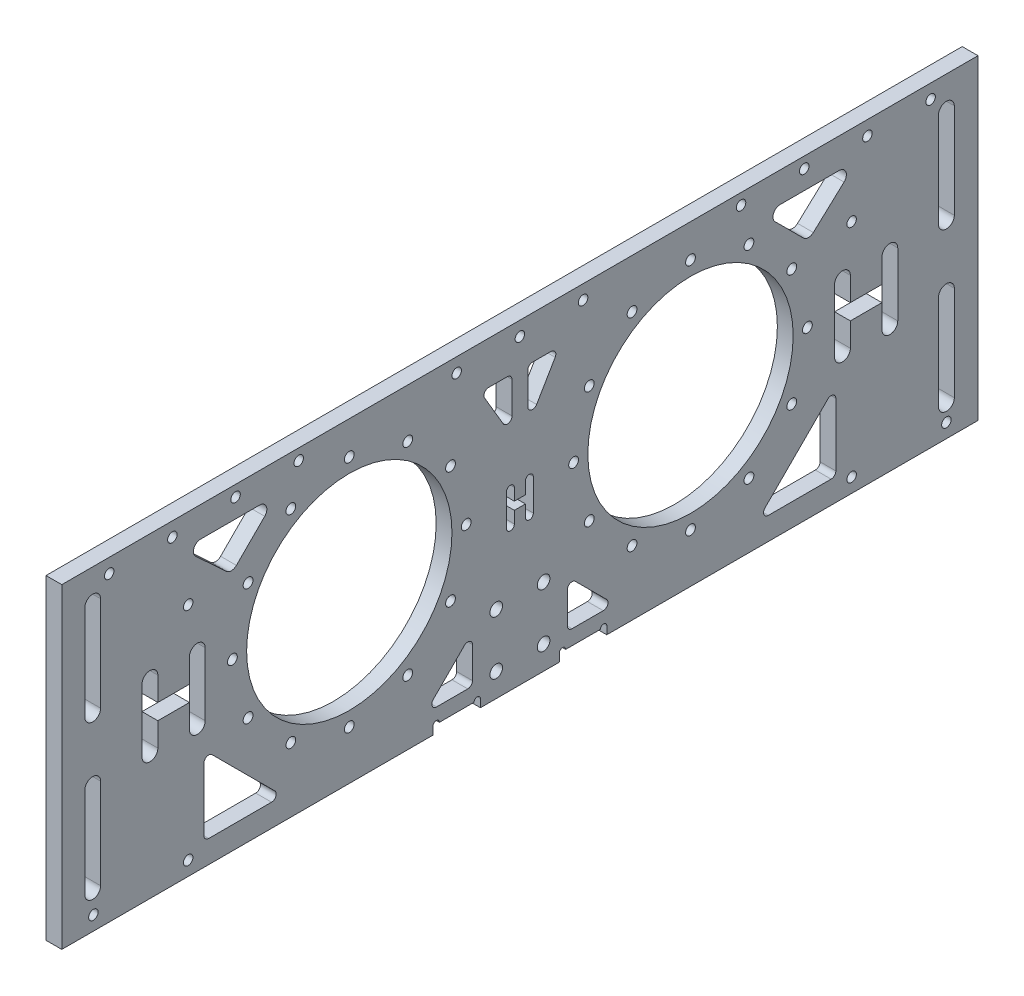
SolidWorks part; units mm, degrees
material "6061 合金"
ref_plane "前视基准面" through (0, 0, 0) normal (0, 0, 1) x (1, 0, 0)
ref_plane "上视基准面" through (0, 0, 0) normal (0, 1, 0) x (1, 0, 0)
ref_plane "右视基准面" through (0, 0, 0) normal (1, 0, 0) x (0, 0, -1)
sketch "草图1" plane through (0, 0, 0) normal (1, 0, 0) x (0, 0, -1)
  line L0 (54, 48) -> (54, -53) construction
  line L1 (-90, -53) -> (198, -53)
  line L2 (-90, -53) -> (-90, 48)
  line L3 (-90, 48) -> (198, 48)
  line L4 (198, -53) -> (198, 48)
  line L5 (-36, 44) -> (-16, 44) construction
  line L6 (46.5, -45) -> (61.5, -45) construction
  line L7 (46.5, -45) -> (46.5, -28) construction
  line L8 (46.5, -28) -> (61.5, -28) construction
  line L9 (61.5, -45) -> (61.5, -28) construction
  line L10 (46.5, -45) -> (61.5, -28) construction
  line L11 (46.5, -28) -> (61.5, -45) construction
  line L12 (144, 44) -> (124, 44) construction
  circle A0 centre (0, 0) radius 32.5
  circle A1 centre (0, 0) radius 37 construction
  circle A2 centre (0, 37) radius 1.55
  circle A3 centre (18.5, 32.0429) radius 1.55
  circle A4 centre (32.0429, 18.5) radius 1.55
  circle A5 centre (37, 0) radius 1.55
  circle A6 centre (32.0429, -18.5) radius 1.55
  circle A7 centre (18.5, -32.0429) radius 1.55
  circle A8 centre (0, -37) radius 1.55
  circle A9 centre (-18.5, -32.0429) radius 1.55
  circle A10 centre (-32.0429, -18.5) radius 1.55
  circle A11 centre (-37, 0) radius 1.55
  circle A12 centre (-32.0429, 18.5) radius 1.55
  circle A13 centre (-18.5, 32.0429) radius 1.55
  circle A14 centre (126.5, 32.0429) radius 1.55
  circle A15 centre (140.0429, 18.5) radius 1.55
  circle A16 centre (145, 0) radius 1.55
  circle A17 centre (140.0429, -18.5) radius 1.55
  circle A18 centre (126.5, -32.0429) radius 1.55
  circle A19 centre (108, -37) radius 1.55
  circle A20 centre (89.5, -32.0429) radius 1.55
  circle A21 centre (75.9571, -18.5) radius 1.55
  circle A22 centre (71, 0) radius 1.55
  circle A23 centre (75.9571, 18.5) radius 1.55
  circle A24 centre (89.5, 32.0429) radius 1.55
  circle A25 centre (108, 37) radius 1.55
  circle A26 centre (108, 0) radius 37 construction
  circle A27 centre (108, 0) radius 32.5
  circle A28 centre (0, 0) radius 46 construction
  circle A29 centre (108, 0) radius 46 construction
  circle A30 centre (61.5, -28) radius 2
  circle A31 centre (46.5, -28) radius 2
  circle A32 centre (46.5, -45) radius 2
  circle A33 centre (61.5, -45) radius 2
  circle A34 centre (-16, 44) radius 1.5
  circle A35 centre (-36, 44) radius 1.5
  circle A36 centre (124, 44) radius 1.5
  circle A37 centre (144, 44) radius 1.5
  point P63 (54, -36.5)
  dimension "D1" = 65
  dimension "D2" = 74
  dimension "D4" = 3.1
  dimension "D9" = 92
  dimension "D13" = 4
  dimension "D17" = 3
  dimension "D5" = 53
  dimension "D6" = 48
  dimension "D7" = 90
  dimension "D8" = 108
  dimension "D10" = 25
  dimension "D11" = 17
  dimension "D12" = 15
  dimension "D14" = 70
  dimension "D15" = 20
  dimension "D16" = 4
  dimension "D3" = 12
extrude "凸台-拉伸1" add sketch "草图1" along normal blind 5
sketch "草图2" plane through (5, 0, 0) normal (1, 0, 0) x (0, 0, -1)
  line L0 (-76, 43) -> (-56, 43) construction
  line L1 (54, 48) -> (54, -53) construction
  line L2 (198, 48) -> (-90, 48) construction
  line L3 (-90, -53) -> (198, -53) construction
  line L4 (184, 43) -> (164, 43) construction
  line L5 (-90, 48) -> (-90, -53) construction
  line L6 (34, 43) -> (54, 43) construction
  circle A0 centre (-76, 43) radius 1.5
  circle A1 centre (-56, 43) radius 1.5
  circle A2 centre (164, 43) radius 1.5
  circle A3 centre (184, 43) radius 1.5
  circle A4 centre (34, 43) radius 1.5
  circle A5 centre (54, 43) radius 1.5
  circle A6 centre (74, 43) radius 1.5
  dimension "D1" = 14
  dimension "D4" = 3
  dimension "D6" = 3
  dimension "D2" = 20
  dimension "D3" = 5
  dimension "D5" = 20
extrude "切除-拉伸1" cut sketch "草图2" against normal through all
sketch "草图3" plane through (5, 0, 0) normal (1, 0, 0) x (0, 0, -1)
  line L0 (-81, -48) -> (-51, -48) construction
  line L1 (-90, 48) -> (-90, -53) construction
  line L2 (-90, -53) -> (198, -53) construction
  line L3 (54, 48) -> (54, -53) construction
  line L4 (198, 48) -> (-90, 48) construction
  line L5 (-81, -48) -> (-81, 22) construction
  line L6 (-81, 22) -> (-51, 22) construction
  line L7 (-51, 22) -> (-51, -48) construction
  line L8 (159, 22) -> (159, -48) construction
  line L9 (189, 22) -> (159, 22) construction
  line L10 (189, -48) -> (189, 22) construction
  line L11 (189, -48) -> (159, -48) construction
  circle A0 centre (-81, -48) radius 1.5
  circle A1 centre (-51, -48) radius 1.5
  circle A2 centre (-81, 22) radius 1.5
  circle A3 centre (-51, 22) radius 1.5
  circle A4 centre (159, 22) radius 1.5
  circle A5 centre (189, 22) radius 1.5
  circle A6 centre (159, -48) radius 1.5
  circle A7 centre (189, -48) radius 1.5
  dimension "D3" = 3
  dimension "D1" = 9
  dimension "D2" = 5
  dimension "D4" = 30
  dimension "D5" = 70
extrude "切除-拉伸2" cut sketch "草图3" against normal blind 10
sketch "草图4" plane through (5, 0, 0) normal (1, 0, 0) x (0, 0, -1)
  line L0 (44.1226, 34) -> (50, 34)
  line L1 (51.5, 32.5) -> (51.5, 22.5085)
  line L2 (48.7071, 21.7479) -> (42.8297, 31.7395)
  line L3 (54, 48) -> (54, -53) construction
  line L4 (198, 48) -> (-90, 48) construction
  line L5 (-90, -53) -> (198, -53) construction
  line L6 (56.5, 32.5) -> (56.5, 22.5085)
  line L7 (63.8774, 34) -> (58, 34)
  line L8 (59.2929, 21.7479) -> (65.1703, 31.7395)
  line L10 (-81, 22) -> (-51, 22) construction
  line L11 (-81, 22) -> (-81, -48) construction
  line L12 (-81, -48) -> (-51, -48) construction
  line L13 (-51, 22) -> (-51, -48) construction
  line L19 (-46, -23.949) -> (-46, -43.8277)
  line L20 (-44.5, -45.3277) -> (-24.6213, -45.3277)
  line L21 (-23.5607, -42.767) -> (-43.4393, -22.8883)
  line L25 (-47.0663, 38) -> (-28.3731, 38)
  line L26 (-26.7654, 34.1187) -> (-35.7353, 25.1488)
  line L27 (-38.8847, 25.0853) -> (-48.608, 34.0552)
  line L34 (27.6213, -45.3277) -> (37.5, -45.3277)
  line L35 (39, -43.8277) -> (39, -33.949)
  line L36 (36.4393, -32.8883) -> (26.5607, -42.767)
  line L37 (71.5607, -32.8883) -> (81.4393, -42.767)
  line L38 (69, -43.8277) -> (69, -33.949)
  line L39 (80.3787, -45.3277) -> (70.5, -45.3277)
  line L40 (159, 22) -> (159, -48) construction
  line L41 (189, -48) -> (159, -48) construction
  line L42 (189, 22) -> (189, -48) construction
  line L43 (189, 22) -> (159, 22) construction
  line L50 (146.8847, 25.0853) -> (156.608, 34.0552)
  line L51 (134.7654, 34.1187) -> (143.7353, 25.1488)
  line L52 (155.0663, 38) -> (136.3731, 38)
  line L56 (131.5607, -42.767) -> (151.4393, -22.8883)
  line L57 (152.5, -45.3277) -> (132.6213, -45.3277)
  line L58 (154, -23.949) -> (154, -43.8277)
  arc A0 (51.5, 22.5085) -> (48.7071, 21.7479) centre (50, 22.5085) cw
  arc A1 (50, 34) -> (51.5, 32.5) centre (50, 32.5) cw
  arc A2 (44.1226, 34) -> (42.8297, 31.7395) centre (44.1226, 32.5) ccw
  arc A3 (58, 34) -> (56.5, 32.5) centre (58, 32.5) ccw
  arc A4 (56.5, 22.5085) -> (59.2929, 21.7479) centre (58, 22.5085) ccw
  arc A5 (63.8774, 34) -> (65.1703, 31.7395) centre (63.8774, 32.5) cw
  arc A14 (-24.6213, -45.3277) -> (-23.5607, -42.767) centre (-24.6213, -43.8277) ccw
  arc A15 (-46, -43.8277) -> (-44.5, -45.3277) centre (-44.5, -43.8277) ccw
  arc A16 (-46, -23.949) -> (-43.4393, -22.8883) centre (-44.5, -23.949) cw
  arc A23 (-28.3731, 38) -> (-26.7654, 34.1187) centre (-28.3731, 35.7264) cw
  arc A24 (-35.7353, 25.1488) -> (-38.8847, 25.0853) centre (-37.343, 26.7565) cw
  arc A25 (-47.0663, 38) -> (-48.608, 34.0552) centre (-47.0663, 35.7264) ccw
  arc A29 (27.6213, -45.3277) -> (26.5607, -42.767) centre (27.6213, -43.8277) cw
  arc A30 (37.5, -45.3277) -> (39, -43.8277) centre (37.5, -43.8277) ccw
  arc A31 (39, -33.949) -> (36.4393, -32.8883) centre (37.5, -33.949) ccw
  arc A32 (69, -33.949) -> (71.5607, -32.8883) centre (70.5, -33.949) cw
  arc A33 (70.5, -45.3277) -> (69, -43.8277) centre (70.5, -43.8277) cw
  arc A34 (80.3787, -45.3277) -> (81.4393, -42.767) centre (80.3787, -43.8277) ccw
  arc A38 (155.0663, 38) -> (156.608, 34.0552) centre (155.0663, 35.7264) cw
  arc A39 (143.7353, 25.1488) -> (146.8847, 25.0853) centre (145.343, 26.7565) ccw
  arc A40 (136.3731, 38) -> (134.7654, 34.1187) centre (136.3731, 35.7264) ccw
  arc A47 (154, -23.949) -> (151.4393, -22.8883) centre (152.5, -23.949) ccw
  arc A48 (154, -43.8277) -> (152.5, -45.3277) centre (152.5, -43.8277) cw
  arc A49 (132.6213, -45.3277) -> (131.5607, -42.767) centre (132.6213, -43.8277) cw
  point P11 (51.5, 17)
  point P14 (51.5, 34)
  point P17 (41.5, 34)
  point P73 (-21, -45.3277)
  point P76 (-46, -45.3277)
  point P79 (-46, -20.3277)
  point P97 (-22.8841, 38)
  point P102 (-52.8841, 38)
  point P105 (-52, 26)
  point P108 (-77, 26)
  point P111 (-77, 38)
  point P115 (24, -45.3277)
  point P118 (39, -45.3277)
  point P130 (69, -45.3277)
  point P131 (84, -45.3277)
  point P199 (185, 38)
  point P200 (185, 26)
  point P201 (160, 26)
  point P202 (160.8841, 38)
  point P203 (130.8841, 38)
  point P207 (154, -20.3277)
  point P208 (154, -45.3277)
  point P209 (129, -45.3277)
  dimension "D5" = 1.5
  dimension "D26" = 1.5
  dimension "D30" = 1.5
  dimension "D1" = 2.5
  dimension "D2" = 14
  dimension "D3" = 10
  dimension "D4" = 17
  dimension "D14" = 5
  dimension "D15" = 25
  dimension "D16" = 25
  dimension "D17" = 10
  dimension "D19" = 25
  dimension "D21" = 45
  dimension "D22" = 30
  dimension "D27" = 15
  dimension "D28" = 45
  dimension "D29" = 15
extrude "切除-拉伸3" cut sketch "草图4" against normal through all
sketch "草图6" plane through (5, 0, 0) normal (1, 0, 0) x (0, 0, -1)
  line L0 (41.5, -53) -> (41.5, -50)
  line L1 (-90, -53) -> (198, -53) construction
  line L5 (54, 48) -> (54, -53) construction
  line L6 (198, 48) -> (-90, 48) construction
  line L7 (39.5, -50) -> (28.5, -50)
  line L8 (26.5, -50) -> (26.5, -53)
  line L9 (26.5, -53) -> (41.5, -53)
  line L13 (81.5, -53) -> (66.5, -53)
  line L14 (81.5, -50) -> (81.5, -53)
  line L15 (68.5, -50) -> (79.5, -50)
  line L16 (66.5, -53) -> (66.5, -50)
  arc A0 (26.5, -50) -> (28.5, -50) centre (27.5, -50) cw
  arc A1 (41.5, -50) -> (39.5, -50) centre (40.5, -50) ccw
  arc A2 (66.5, -50) -> (68.5, -50) centre (67.5, -50) cw
  arc A3 (81.5, -50) -> (79.5, -50) centre (80.5, -50) ccw
  dimension "D4" = 1
  dimension "D1" = 25
  dimension "D2" = 3
  dimension "D3" = 15
extrude "切除-拉伸4" cut sketch "草图6" against normal through all
sketch "草图8" plane through (5, 0, 0) normal (1, 0, 0) x (0, 0, -1)
  line L0 (-90, -53) -> (-91, -53)
  line L1 (-91, -53) -> (-91, 48)
  line L2 (-91, 48) -> (-90, 48)
  line L3 (-90, 48) -> (-90, -53)
  line L4 (198, -53) -> (199, -53)
  line L5 (199, -53) -> (199, 48)
  line L6 (199, 48) -> (198, 48)
  line L7 (198, 48) -> (198, -53)
extrude "凸台-拉伸3" add sketch "草图8" against normal up to surface (5 mm away) up to face at (0, -38.625, -54)
sketch "草图9" plane through (5, 0, 0) normal (1, 0, 0) x (0, 0, -1)
  line L0 (-91, 48) -> (-91, 47.5)
  line L1 (-91, 48) -> (-91, -53) construction
  line L2 (-91, 47.5) -> (199, 47.5)
  line L3 (199, -53) -> (199, 48) construction
  line L4 (199, 47.5) -> (199, 48)
  line L5 (199, 48) -> (-91, 48)
  line L6 (-91, -53) -> (-91, -52.5)
  line L7 (-91, -52.5) -> (199, -52.5)
  line L8 (199, -52.5) -> (199, -53)
  line L9 (199, -53) -> (-91, -53)
extrude "切除-拉伸5" cut sketch "草图9" against normal blind 10
sketch "草图10" plane through (0, 0, 0) normal (-1, 0, 0) x (0, 0, 1)
  line L0 (91, -2.5) -> (81.2144, -2.5)
  line L1 (91, 47.5) -> (91, -52.5) construction
  line L2 (81.2144, -2.5) -> (81.2144, 7.5)
  line L3 (81.2144, -2.5) -> (81.2144, -12.5)
  line L4 (81.2144, 7.5) -> (81.2144, 37.5) construction
  line L5 (78.7144, 7.5) -> (78.7144, 37.5)
  line L6 (83.7144, 7.5) -> (83.7144, 37.5)
  line L7 (81.2144, -12.5) -> (81.2144, -41.1754) construction
  line L8 (83.7144, -12.5) -> (83.7144, -41.1754)
  line L9 (78.7144, -12.5) -> (78.7144, -41.1754)
  line L10 (-199, -2.5) -> (-189, -2.5)
  line L11 (-199, -52.5) -> (-199, 47.5) construction
  line L12 (-189, -2.5) -> (-189, 7.5)
  line L13 (-189, -2.5) -> (-189, -12.5)
  line L14 (-189, 7.5) -> (-189, 37.5) construction
  line L15 (-191.5, 7.5) -> (-191.5, 37.5)
  line L16 (-186.5, 7.5) -> (-186.5, 37.5)
  line L17 (-189, -12.5) -> (-189, -42.5) construction
  line L18 (-186.5, -12.5) -> (-186.5, -42.5)
  line L19 (-191.5, -12.5) -> (-191.5, -42.5)
  arc A0 (78.7144, 7.5) -> (83.7144, 7.5) centre (81.2144, 7.5) ccw
  arc A1 (83.7144, 37.5) -> (78.7144, 37.5) centre (81.2144, 37.5) ccw
  arc A2 (83.7144, -12.5) -> (78.7144, -12.5) centre (81.2144, -12.5) ccw
  arc A3 (78.7144, -41.1754) -> (83.7144, -41.1754) centre (81.2144, -41.1754) ccw
  arc A4 (-191.5, 7.5) -> (-186.5, 7.5) centre (-189, 7.5) ccw
  arc A5 (-186.5, 37.5) -> (-191.5, 37.5) centre (-189, 37.5) ccw
  arc A6 (-186.5, -12.5) -> (-191.5, -12.5) centre (-189, -12.5) ccw
  arc A7 (-191.5, -42.5) -> (-186.5, -42.5) centre (-189, -42.5) ccw
  point P4 (81.2144, 22.5)
  point P12 (81.2144, -26.8377)
  point P24 (-189, 22.5)
  point P30 (-189, -27.5)
  dimension "D1" = 10
  dimension "D2" = 10
  dimension "D3" = 10
  dimension "D4" = 10
  dimension "D5" = 10
extrude "切除-拉伸6" cut sketch "草图10" against normal blind 10 contours L16 A5 L15 A4 | L19 A7 L18 A6 | L6 A1 L5 A0 | L9 A3 L8 A2 region at (0, 22.5, 81.2144) region at (0, -26.8377, 81.2144) region at (0, 22.5, -189) region at (0, -27.5, -189)
sketch "草图11" plane through (0, 0, 0) normal (-1, 0, 0) x (0, 0, 1)
  line L0 (-199, -2.5) -> (-171.1008, -2.5)
  line L1 (-199, -52.5) -> (-199, 47.5) construction
  line L2 (-171.1008, -2.5) -> (-171.1008, 7.5)
  line L3 (-171.1008, -2.5) -> (-171.1008, -12.5)
  line L4 (-171.1008, -2.5) -> (-156.1008, -2.5)
  line L5 (-156.1008, -2.5) -> (-156.1008, 7.5)
  line L6 (-156.1008, -2.5) -> (-156.1008, -12.5)
  line L7 (-171.1008, 7.5) -> (-171.1008, -12.5) construction
  line L10 (-156.1008, 7.5) -> (-156.1008, -12.5) construction
  line L11 (-153.6008, 7.5) -> (-153.6008, -12.5)
  line L12 (-158.6008, 7.5) -> (-158.6008, -12.5)
  line L13 (-168.6008, 7.5) -> (-168.6008, -12.5)
  line L14 (-173.6008, 7.5) -> (-173.6008, -12.5)
  line L15 (-171.1008, -2.5) -> (-156.1008, -2.5) construction
  line L16 (-171.1008, 0) -> (-156.1008, 0)
  line L17 (-171.1008, -5) -> (-156.1008, -5)
  line L18 (-54, 47.5) -> (-54, -52.5)
  line L19 (-199, 47.5) -> (91, 47.5) construction
  line L20 (-41.5, -52.5) -> (-66.5, -52.5) construction
  line L21 (48.1008, 7.5) -> (48.1008, -12.5) construction
  line L22 (45.6008, 7.5) -> (45.6008, -12.5)
  line L23 (50.6008, 7.5) -> (50.6008, -12.5)
  line L24 (63.1008, 7.5) -> (63.1008, -12.5) construction
  line L25 (60.6008, 7.5) -> (60.6008, -12.5)
  line L26 (65.6008, 7.5) -> (65.6008, -12.5)
  line L27 (63.1008, -2.5) -> (48.1008, -2.5) construction
  line L28 (63.1008, 0) -> (48.1008, 0)
  line L29 (63.1008, -5) -> (48.1008, -5)
  arc A2 (-153.6008, 7.5) -> (-158.6008, 7.5) centre (-156.1008, 7.5) ccw
  arc A3 (-158.6008, -12.5) -> (-153.6008, -12.5) centre (-156.1008, -12.5) ccw
  arc A4 (-168.6008, 7.5) -> (-173.6008, 7.5) centre (-171.1008, 7.5) ccw
  arc A5 (-173.6008, -12.5) -> (-168.6008, -12.5) centre (-171.1008, -12.5) ccw
  arc A6 (-171.1008, 0) -> (-171.1008, -5) centre (-171.1008, -2.5) ccw
  arc A7 (-156.1008, -5) -> (-156.1008, 0) centre (-156.1008, -2.5) ccw
  arc A8 (45.6008, 7.5) -> (50.6008, 7.5) centre (48.1008, 7.5) cw
  arc A9 (50.6008, -12.5) -> (45.6008, -12.5) centre (48.1008, -12.5) cw
  arc A10 (60.6008, 7.5) -> (65.6008, 7.5) centre (63.1008, 7.5) cw
  arc A11 (65.6008, -12.5) -> (60.6008, -12.5) centre (63.1008, -12.5) cw
  arc A12 (63.1008, 0) -> (63.1008, -5) centre (63.1008, -2.5) cw
  arc A13 (48.1008, -5) -> (48.1008, 0) centre (48.1008, -2.5) cw
  point P4 (-171.1008, -2.5)
  point P14 (-156.1008, -2.5)
  point P19 (-163.6008, -2.5)
  point P32 (48.1008, -2.5)
  point P39 (63.1008, -2.5)
  point P46 (55.6008, -2.5)
  dimension "D1" = 15
extrude "切除-拉伸7" cut sketch "草图11" against normal blind 10 contours L16 L13 L4 L12 | L16 L2 L4 L13 | A6 L16 L13 A4 L14 | A6 L14 A5 L13 L17 | L3 L17 L13 L4 | L0 A6 L3 | L2 A6 L0 | L12 L17 L6 L4 | A7 L5 L6 | L16 L12 L4 L5 | A7 L11 A2 L12 L16 | A7 L17 L12 A3 L11 | L22 A9 L23 A8 | L28 A13 L29 A12 | L25 A11 L26 A10 | L17 A7 L16 A6 region at (0, -1.439, -172.1618) region at (0, -9.6019, -171.1543) region at (0, 4.6019, -171.1543) region at (0, -3.561, -172.1618) region at (0, -3.75, -169.8508) region at (0, -1.25, -169.8508) region at (0, -1.25, -163.6008) region at (0, -1.25, -157.3508) region at (0, -3.75, -157.3508) region at (0, 4.6019, -156.0473) region at (0, -9.6019, -156.0473) region at (0, -2.5, -155.0398)
sketch "草图12" plane through (5, 0, 0) normal (1, 0, 0) x (0, 0, -1)
  line L0 (54, 47.5) -> (54, -52.5)
  line L1 (54, -2.5) -> (52.25, -2.5)
  line L2 (51, -1.25) -> (51, 2.5)
  line L3 (-91, 47.5) -> (199, 47.5) construction
  line L4 (66.5, -52.5) -> (41.5, -52.5) construction
  line L5 (54, -2.5) -> (57.75, -2.5)
  line L6 (57, -1.25) -> (57, 2.5)
  line L7 (57, -2.5) -> (57, -7.5)
  line L8 (51, -2.5) -> (51, -7.5)
  line L9 (51, 2.5) -> (51, -1.25) construction
  line L10 (52.25, 2.5) -> (52.25, -1.25)
  line L11 (49.75, 2.5) -> (49.75, -7.5)
  line L12 (57, 2.5) -> (57, -1.25) construction
  line L13 (58.25, 2.5) -> (58.25, -7.5)
  line L14 (55.75, 2.5) -> (55.75, -1.25)
  line L15 (52.25, -2.5) -> (57.75, -2.5) construction
  line L16 (52.25, -1.25) -> (55.75, -1.25)
  line L17 (52.25, -3.75) -> (55.75, -3.75)
  line L18 (52.25, -3.75) -> (52.25, -7.5)
  line L19 (51, -2.5) -> (51, -7.5) construction
  line L20 (57, -2.5) -> (57, -7.5) construction
  line L21 (55.75, -3.75) -> (55.75, -7.5)
  arc A0 (52.25, 2.5) -> (49.75, 2.5) centre (51, 2.5) ccw
  arc A1 (49.75, -7.5) -> (52.25, -7.5) centre (51, -7.5) ccw
  arc A2 (58.25, 2.5) -> (55.75, 2.5) centre (57, 2.5) ccw
  arc A3 (55.75, -7.5) -> (58.25, -7.5) centre (57, -7.5) ccw
  point P13 (49, -2.5)
  point P20 (59, -2.5)
  point P25 (54, -2.5)
  dimension "D1" = 3
  dimension "D2" = 5
  dimension "D3" = 5
  dimension "D4" = 5
  dimension "D5" = 5
  dimension "D6" = 3
extrude "切除-拉伸8" cut sketch "草图12" against normal blind 10 contours L21 A3 L13 A2 L14 L16 L0 L17 | L11 A1 L18 L17 L0 L16 L10 A0 region at (5, -1.382, -54.875) region at (5, -2.5, -51.2712)
